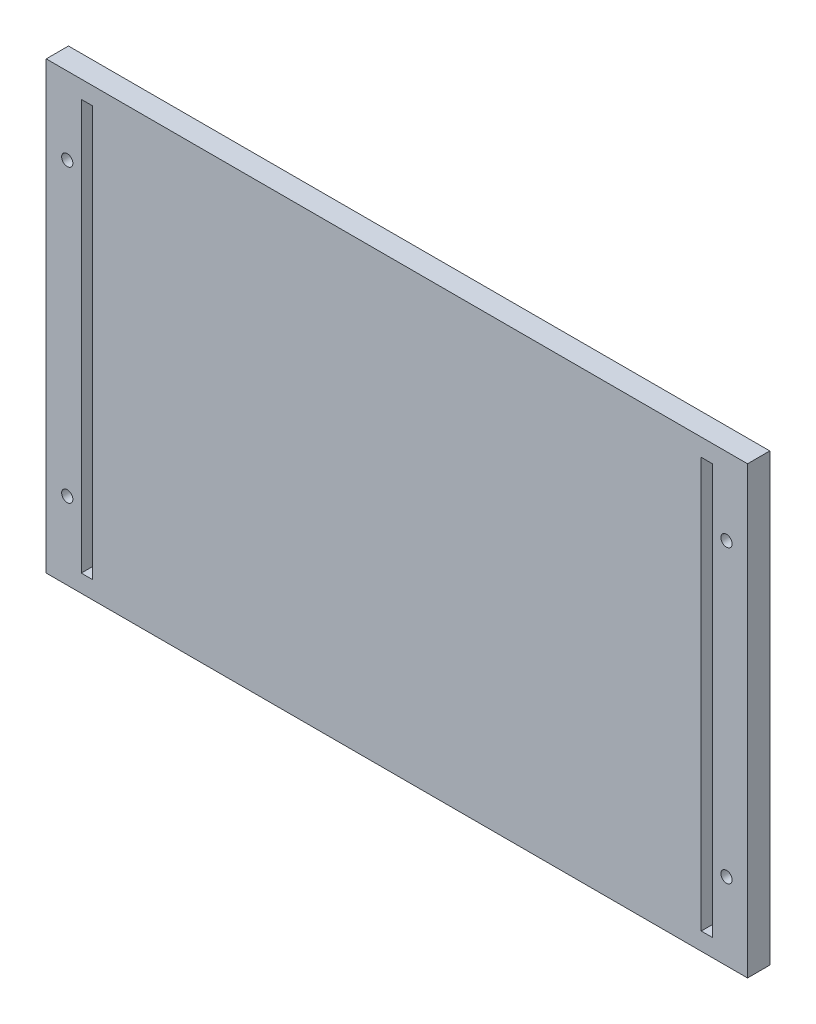
SolidWorks part; units mm, degrees
ref_plane "Front Plane" through (0, 0, 0) normal (0, 0, 1) x (1, 0, 0)
ref_plane "Top Plane" through (0, 0, 0) normal (0, 1, 0) x (1, 0, 0)
ref_plane "Right Plane" through (0, 0, 0) normal (1, 0, 0) x (0, 0, -1)
sketch "Sketch1" plane through (0, 0, 0) normal (0, 0, 1) x (1, 0, 0)
  line L0 (100, 127) -> (100, 0) construction
  line L1 (0, 0) -> (200, 0)
  line L2 (0, 0) -> (0, 127)
  line L3 (0, 127) -> (200, 127)
  line L4 (200, 0) -> (200, 127)
  line L5 (0, 63.5) -> (200, 63.5) construction
  circle A3 centre (6, 105) radius 1.6
  circle A7 centre (194, 105) radius 1.6
  circle A8 centre (194, 22) radius 1.6
  circle A9 centre (6, 22) radius 1.6
  dimension "D11" = 3.2
  dimension "D1" = 127
  dimension "D2" = 200
  dimension "D12" = 6
  dimension "D13" = 22
extrude "Wall" add sketch "Sketch1" along normal blind 6.35
sketch "Sketch2" [suppressed] plane through (0, 0, 6.35) normal (0, 0, 1) x (1, 0, 0)
  line L0 (135.35, 127) -> (135.35, 98.425) construction
  line L1 (270.7, 127) -> (0, 127) construction
  line L2 (135.35, 98.425) -> (66.6667, 98.425) construction
  line L3 (135.35, 98.425) -> (204.0333, 98.425) construction
  line L4 (0, 127) -> (0, 0) construction
  circle A0 centre (135.35, 98.425) radius 3.9687
  circle A1 centre (66.6667, 98.425) radius 3.9688
  circle A2 centre (204.0333, 98.425) radius 3.9687
  dimension "D2" = 7.9375
  dimension "D1" = 28.575
  dimension "D3" = 66.6667
extrude "RodSupportCutouts" [suppressed] cut sketch "Sketch2" against normal up to next
sketch "Sketch3" [suppressed] plane through (0, 0, 6.35) normal (0, 0, 1) x (1, 0, 0)
  line L1 (25.4, 88.9) -> (245.3, 88.9)
  line L2 (25.4, 88.9) -> (25.4, 114.3)
  line L3 (25.4, 114.3) -> (245.3, 114.3)
  line L4 (245.3, 88.9) -> (245.3, 114.3)
  line L5 (25.4, 88.9) -> (245.3, 114.3) construction
  line L6 (25.4, 114.3) -> (245.3, 88.9) construction
  line L7 (270.7, 127) -> (0, 127) construction
  line L8 (0, 127) -> (0, 0) construction
  point P0 (135.35, 101.6)
  point P9 (135.35, 127)
  dimension "D1" = 25.4
  dimension "D2" = 25.4
  dimension "D3" = 25.4
extrude "CannulaLargeCutout" [suppressed] cut sketch "Sketch3" against normal up to next
sketch "Sketch4" [suppressed] plane through (0, 0, 9.525) normal (0, 0, 1) x (1, 0, 0)
  line L0 (6, 103.5) -> (194, 103.5) construction
  line L1 (6, 105) -> (6, 22) construction
  line L2 (194, 105) -> (194, 22) construction
  line L3 (200, 127) -> (0, 127) construction
  line L4 (0, 127) -> (0, 0) construction
  circle A0 centre (60, 103.5) radius 6.35
  circle A1 centre (20, 103.5) radius 6.35
  circle A2 centre (100, 103.5) radius 6.35
  circle A3 centre (140, 103.5) radius 6.35
  circle A4 centre (60, 63.5) radius 6.35
  circle A5 centre (100, 63.5) radius 6.35
  circle A6 centre (140, 63.5) radius 6.35
  circle A7 centre (60, 23.5) radius 6.35
  circle A8 centre (100, 23.5) radius 6.35
  circle A9 centre (140, 23.5) radius 6.35
  circle A10 centre (20, 63.5) radius 6.35
  circle A11 centre (20, 23.5) radius 6.35
  circle A12 centre (180, 103.5) radius 6.35
  circle A13 centre (180, 63.5) radius 6.35
  circle A14 centre (180, 23.5) radius 6.35
  point P42 (100, 127)
  point P45 (0, 63.5)
  dimension "D3" = 12.7
  dimension "D1" = 5
  dimension "D2" = 3
extrude "CannulaHoles" [suppressed] cut sketch "Sketch4" against normal up to next
ref_plane "LeftBoundary" [suppressed] through (25.4, 0, 0) normal (-1, 0, 0) x (0, 0, 1)
ref_plane "RightBoundary" [suppressed] through (245.3, 0, 0) normal (1, 0, 0) x (0, 0, -1)
ref_plane "TopBoundary" [suppressed] through (0, 101.6, 0) normal (0, 1, 0) x (1, 0, 0)
ref_plane "BottomBoundary" [suppressed] through (0, 25.4, 0) normal (0, -1, 0) x (-1, 0, 0)
sketch "Sketch5" [suppressed] plane through (0, 0, 6.35) normal (0, 0, 1) x (1, 0, 0)
  line L4 (25.4, 3.4925) -> (25.4, -3.4925) construction
  line L5 (3.4925, 101.6) -> (-3.4925, 101.6) construction
  circle A0 centre (25.4, 101.6) radius 3.9687
  dimension "D1" = 7.9375
extrude "RodSupportCutout" [suppressed] cut sketch "Sketch5" along normal blind 3.35 from surface starting at face at (4.4, 22, 0)
pattern_linear "SupportPattern" [suppressed] count 7 spacing 36.65 count 5 spacing 19.05 of bodies 105
sketch "Sketch6" plane through (0, 0, 6.35) normal (0, 0, 1) x (1, 0, 0)
  line L0 (10, 122) -> (13.2, 122)
  line L1 (186.8, 122) -> (190, 122)
  line L2 (186.8, 122) -> (186.8, 5)
  line L3 (186.8, 5) -> (190, 5)
  line L4 (190, 122) -> (190, 5)
  line L5 (10, 122) -> (10, 5)
  line L6 (10, 5) -> (13.2, 5)
  line L7 (13.2, 122) -> (13.2, 5)
  line L8 (0, 127) -> (0, 0) construction
  line L9 (0, 0) -> (200, 0) construction
  line L10 (200, 0) -> (200, 127) construction
  line L11 (0, 0) -> (200, 0) construction
  point P7 (200, 57)
  dimension "D1" = 117
  dimension "D2" = 5
  dimension "SlitDiameter" = 3.2
  dimension "D4" = 10
  dimension "D5" = 10
  dimension "D6" = 5
  dimension "D7" = 117
  dimension "D3" = 3.2
extrude "Cut-Extrude1" cut sketch "Sketch6" against normal through all
equation "\"Length\"= 283mm"
equation "\"Width\"= 225mm"
equation "\"WallThickness\"= 0.25in"
equation "\"UpperWaterJacketThickness\"= 28mm"
equation "\"SpacerHeight\"= 80.2mm"
equation "\"SpacerCornerWidth\"= 10mm"
equation "\"SpacerCornerHeight\"= 60.16mm"
equation "\"SpacerPegDiameter\"= 10mm"
equation "\"SpacerPegHeight\"= 10mm"
equation "\"TubingShort\"= 110mm"
equation "\"TubingLong\"= 175mm"
equation "\"PlateLength\"= 252mm"
equation "\"PlateWidth\"= 190mm"
equation "\"PlateHoleDiameter\"= 5.9mm"
equation "\"PlateHoleBottom\"= 2mm"
equation "\"PlateHoleSide\"= 1.55mm"
equation "\"PlateHoleSpacing\"= 3.1mm"
equation "\"PlateThickness\"= 1.55mm"
equation "\"ReservoirBottom\"= 12.5mm"
equation "\"ReservoirSupportWidth\"= 12mm"
equation "\"ReservoirSupportHeight\"= 15.1mm"
equation "\"ReservoirSupportPlacementHeight\"= 50mm"
equation "\"ReservoirHoleDiameter\"= 12.7mm"
equation "\"ReservoirHoleRight\"= 25mm"
equation "\"ReservoirHoleTop\"= \"ReservoirSupportPlacementHeight\""
equation "\"ReservoirHeight\"= 90mm"
equation "\"ReservoirPortBottom\"= 4mm"
equation "\"ReservoirPortTop\"= 10mm"
equation "\"ReservoirPortWidth\"= 101mm"
equation "\"CustomSpacerHeight\"= 5in"
equation "\"CustomSpacerRodHoleHeight\"= .75in"
equation "\"CustomSpacerRodHoleDiameter\"= .3125in"
equation "\"ScrewBlockSide\"= 12mm"
equation "\"ScrewBlockUpperHeight\"= 16mm"
equation "\"ScrewBlockLowerHeight\"= 16mm"
equation "\"InternalLength\"= 258mm"
equation "\"InternalWidth\"= 200mm"
equation "\"CustomSpacerPegHeight\"= 1in"
equation "\"CustomSpacerScrewBore\"=3.2mm"
equation "\"CustomSpacerScrewDepth\"=10mm"
equation "\"D1@Sketch1\"=\"CustomSpacerHeight\""
equation "\"D2@Sketch1\"=\"WallLength\""
equation "\"D11@Sketch1\"=\"CustomSpacerScrewBore\""
equation "\"D12@Sketch1\"   = \"ScrewBlockSide\"/2"
equation "\"D13@Sketch1\"=\"ScrewBlockUpperHeight\"+\"ScrewBlockSide\"/2"
equation "\"D1@Wall\" = \"WallThickness\""
equation "\"D1@Sketch2\"=\"CustomSpacerRodHoleHeight\" + \"CustomSpacerRodHoleDiameter\" +0.0625in"
equation "\"D2@Sketch2\"=\"CustomSpacerRodHoleDiameter\""
equation "\"D3@Sketch2\"=\"InternalWidth\" / 3"
equation "\"D1@Sketch3\"=1in"
equation "\"WallLength\"= \"InternalWidth\""
equation "\"D1@Sketch5\"=\"CustomSpacerRodHoleDiameter\""
equation "\"D1@RodSupportCutout\"      = \"WallThickness\" - 3"
equation "\"SlitDiameter@Sketch6\" = \"CustomSpacerScrewBore\""
equation "\"D3@Sketch6\"=\"CustomSpacerScrewBore\""
